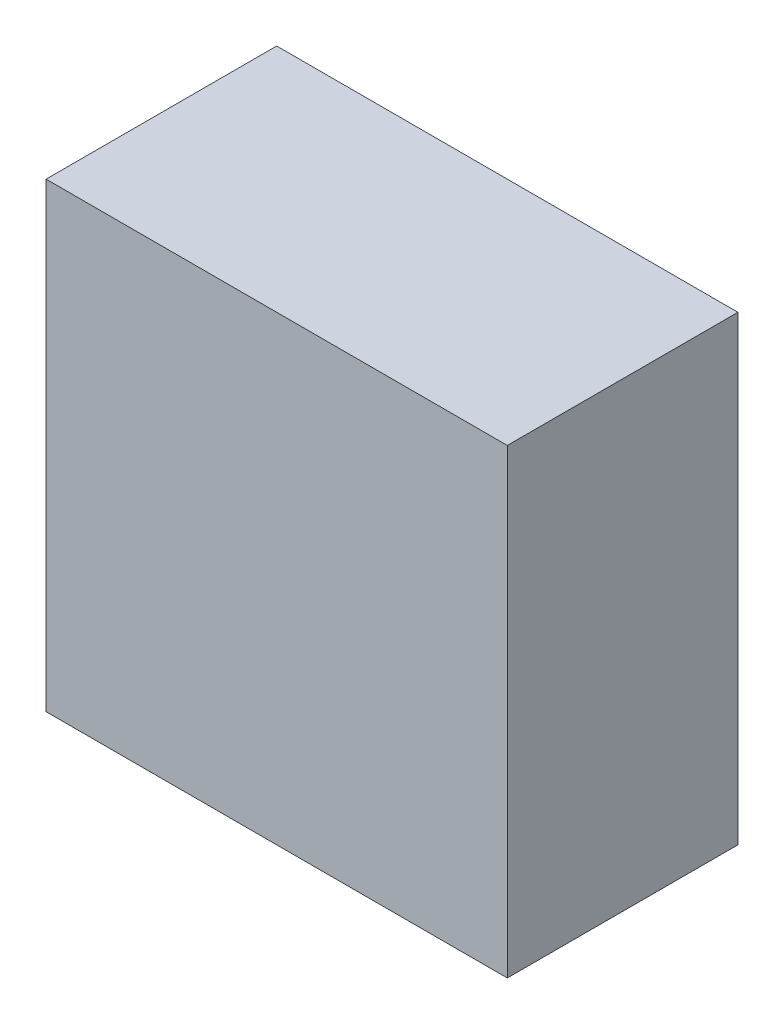
SolidWorks part; units mm, degrees
ref_plane "Front Plane" through (0, 0, 0) normal (0, 0, 1) x (1, 0, 0)
ref_plane "Top Plane" through (0, 0, 0) normal (0, 1, 0) x (1, 0, 0)
ref_plane "Right Plane" through (0, 0, 0) normal (1, 0, 0) x (0, 0, -1)
sketch "Sketch1" plane through (0, 0, 0) normal (0, 0, 1) x (1, 0, 0)
  line L1 (0, 0) -> (160, 0)
  line L2 (0, 0) -> (0, 160)
  line L3 (0, 160) -> (160, 160)
  line L4 (160, 0) -> (160, 160)
extrude "Boss-Extrude1" add sketch "Sketch1" along normal blind 80
